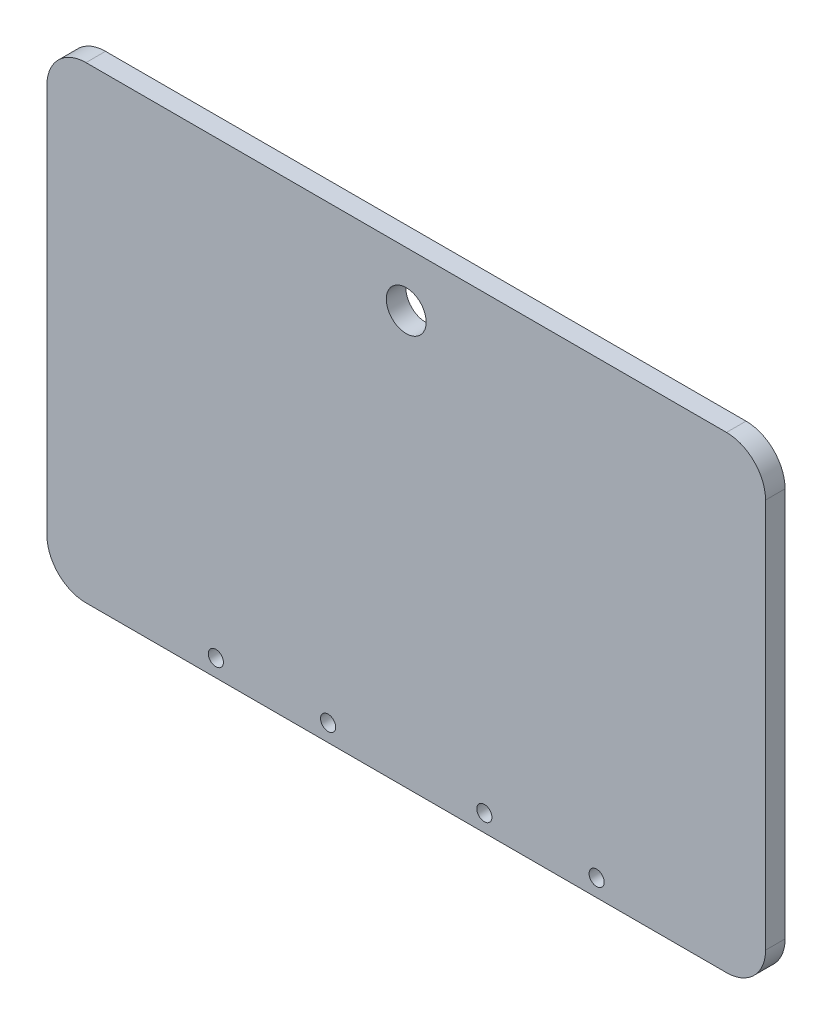
SolidWorks part; units mm, degrees
material "Acrylic (Medium-high impact)"
ref_plane "Front Plane" through (0, 0, 0) normal (0, 0, 1) x (1, 0, 0)
ref_plane "Top Plane" through (0, 0, 0) normal (0, 1, 0) x (1, 0, 0)
ref_plane "Right Plane" through (0, 0, 0) normal (1, 0, 0) x (0, 0, -1)
sketch "Sketch1" plane through (0, 0, 0) normal (0, 0, 1) x (1, 0, 0)
  line L1 (233.68, 152.146) -> (0, 152.146)
  line L2 (233.68, 152.146) -> (233.68, 0)
  line L3 (233.68, 0) -> (0, 0)
  line L4 (0, 152.146) -> (0, 0)
  line L5 (233.68, 152.146) -> (0, 0) construction
  line L6 (233.68, 0) -> (0, 152.146) construction
  point P0 (116.84, 76.073)
  dimension "D1" = 152.146
  dimension "D2" = 233.68
extrude "Boss-Extrude1" add sketch "Sketch1" along normal blind 6.35
hole_wizard "#8 Clearance Hole1" positions "Sketch6" profile "Sketch7" hole size "#8" standard "ANSI Inch" end condition through all
sketch "Sketch6" plane through (0, 0, 6.35) normal (0, 0, 1) x (1, 0, 0)
  line L2 (0, 0) -> (233.68, 0) construction
  line L3 (91.44, 5.588) -> (142.24, 5.588) construction
  line L5 (116.84, 0) -> (116.84, 5.588) construction
  line L6 (54.9275, 5.588) -> (91.44, 5.588) construction
  line L9 (142.24, 5.588) -> (178.7525, 5.588) construction
  point P0 (54.9275, 5.588)
  point P11 (91.44, 5.588)
  point P13 (142.24, 5.588)
  point P15 (178.7525, 5.588)
  dimension "D1" = 36.5125
  dimension "D2" = 5.588
  dimension "D5" = 50.8
sketch "Sketch7" plane through (54.9275, 5.588, 6.35) normal (1, 0, 0) x (0, -1, 0)
  line L0 (0, 0) -> (0, 6.35)
  line L1 (0, 6.35) -> (2.4574, 6.35)
  line L2 (2.4574, 6.35) -> (2.4574, 0)
  line L5 (2.4574, 0) -> (0, 0)
  line L11 (0, -6.35) -> (0, 107.95) construction
  dimension "Thru Hole Dia." = 4.9149
  dimension "Thru Hole Depth" = 6.35
sketch "Sketch8" plane through (0, 0, 6.35) normal (0, 0, 1) x (1, 0, 0)
  line L0 (0, 0) -> (233.68, 0) construction
  line L1 (233.68, 152.146) -> (0, 152.146) construction
  circle A0 centre (116.84, 134.366) radius 6.477
  point P6 (116.84, 0)
  dimension "D1" = 12.954
  dimension "D2" = 17.78
extrude "Cut-Extrude1" cut sketch "Sketch8" against normal through all
fillet "Fillet1" radius 12.7 4 edges at (233.68, 0, 3.175) (233.68, 152.146, 3.175) (0, 152.146, 3.175) (0, 0, 3.175)
